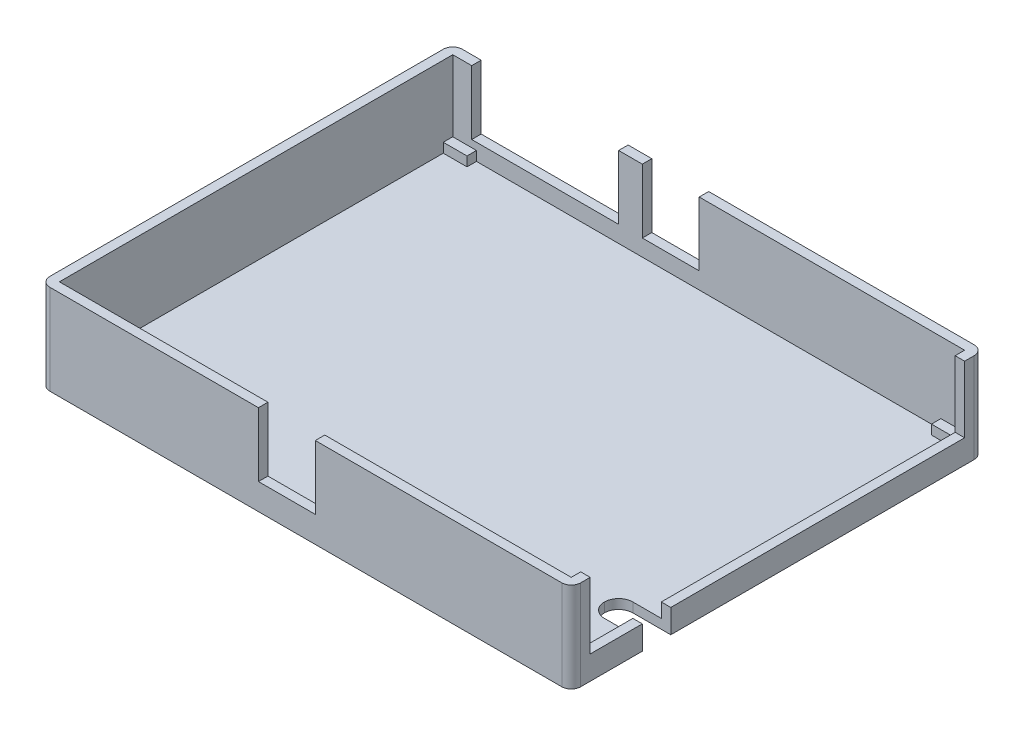
SolidWorks part; units mm, degrees
material "Plain Carbon Steel"
ref_plane "Front Plane" through (0, 0, 0) normal (0, 0, 1) x (1, 0, 0)
ref_plane "Top Plane" through (0, 0, 0) normal (0, 1, 0) x (1, 0, 0)
ref_plane "Right Plane" through (0, 0, 0) normal (1, 0, 0) x (0, 0, -1)
sketch "Sketch1" plane through (0, 0, 0) normal (0, 1, 0) x (1, 0, 0)
  line L1 (0, 0) -> (-112, 0)
  line L2 (0, 0) -> (0, 87)
  line L3 (0, 87) -> (-112, 87)
  line L4 (-112, 0) -> (-112, 87)
  dimension "D1" = 112
  dimension "D2" = 87
extrude "Boss-Extrude1" add sketch "Sketch1" along normal blind 19
sketch "Sketch3" plane through (0, 19, 0) normal (0, 1, 0) x (1, 0, 0)
  line L0 (-112, 87) -> (-112, 0) construction
  line L1 (-110, 85) -> (-2, 85)
  line L2 (-110, 85) -> (-110, 2)
  line L3 (-110, 2) -> (-2, 2)
  line L4 (-2, 85) -> (-2, 2)
  line L5 (0, 87) -> (-112, 87) construction
  line L6 (-112, 0) -> (0, 0) construction
  dimension "D1" = 108
  dimension "D2" = 2
  dimension "D3" = 2
  dimension "D4" = 2
extrude "Cut-Extrude1" cut sketch "Sketch3" against normal blind 17
sketch "Sketch4" plane through (0, 2, 0) normal (0, 1, 0) x (1, 0, 0)
  line L0 (-2, 85) -> (-110, 85) construction
  line L1 (-110, 85) -> (-105, 85)
  line L2 (-110, 85) -> (-110, 83)
  line L3 (-110, 83) -> (-105, 83)
  line L4 (-105, 85) -> (-105, 83)
  line L5 (-110, 85) -> (-110, 2) construction
  dimension "D1" = 0
  dimension "D2" = 0
  dimension "D3" = 5
  dimension "D4" = 2
extrude "Boss-Extrude3" add sketch "Sketch4" along normal blind 2
sketch "Sketch5" plane through (0, 2, 0) normal (0, 1, 0) x (1, 0, 0)
  line L0 (-2, 85) -> (-110, 85) construction
  line L1 (-7, 85) -> (-2, 85)
  line L2 (-7, 85) -> (-7, 83)
  line L3 (-7, 83) -> (-2, 83)
  line L4 (-2, 85) -> (-2, 83)
  line L5 (-2, 2) -> (-2, 85) construction
  dimension "D1" = 5
  dimension "D2" = 2
  dimension "D3" = 0
  dimension "D4" = 0
extrude "Boss-Extrude4" add sketch "Sketch5" along normal blind 2
sketch "Sketch6" plane through (0, 2, 0) normal (0, 1, 0) x (1, 0, 0)
  line L1 (-110, 2) -> (-105, 2)
  line L2 (-110, 2) -> (-110, 4)
  line L3 (-110, 4) -> (-105, 4)
  line L4 (-105, 2) -> (-105, 4)
  dimension "D1" = 5
  dimension "D2" = 2
  dimension "D3" = 0
extrude "Boss-Extrude5" add sketch "Sketch6" along normal blind 2
sketch "Sketch7" plane through (0, 2, 0) normal (0, 1, 0) x (1, 0, 0)
  line L1 (-2, 2) -> (-7, 2)
  line L2 (-2, 2) -> (-2, 4)
  line L3 (-2, 4) -> (-7, 4)
  line L4 (-7, 2) -> (-7, 4)
  dimension "D1" = 5
  dimension "D2" = 2
  dimension "D3" = 0
extrude "Boss-Extrude6" add sketch "Sketch7" along normal blind 2
sketch "Sketch8" plane through (0, 0, 0) normal (0, 0, 1) x (1, 0, 0)
  line L0 (-112, 19) -> (-112, 0) construction
  line L1 (-66, 19) -> (-54, 19)
  line L2 (-66, 19) -> (-66, 5.5)
  line L3 (-66, 5.5) -> (-54, 5.5)
  line L4 (-54, 19) -> (-54, 5.5)
  line L5 (-112, 0) -> (0, 0) construction
  line L8 (-112, 19) -> (0, 19) construction
  dimension "D1" = 46
  dimension "D2" = 12
  dimension "D3" = 5.5
  dimension "D4" = 0
extrude "Cut-Extrude2" cut sketch "Sketch8" against normal blind 2
sketch "Sketch9" plane through (0, 0, -87) normal (0, 0, -1) x (-1, 0, 0)
  line L0 (112, 19) -> (112, 0) construction
  line L1 (106, 19) -> (75, 19)
  line L2 (106, 19) -> (106, 5.5)
  line L3 (106, 5.5) -> (75, 5.5)
  line L4 (75, 19) -> (75, 5.5)
  line L5 (0, 0) -> (112, 0) construction
  line L6 (0, 19) -> (112, 19) construction
  dimension "D1" = 6
  dimension "D2" = 5.5
  dimension "D3" = 0
  dimension "D4" = 31
extrude "Cut-Extrude3" cut sketch "Sketch9" against normal blind 2
sketch "Sketch10" plane through (0, 0, -87) normal (0, 0, -1) x (-1, 0, 0)
  line L0 (75, 19) -> (75, 5.5) construction
  line L1 (70, 19) -> (58, 19)
  line L2 (70, 19) -> (70, 5.5)
  line L3 (70, 5.5) -> (58, 5.5)
  line L4 (58, 19) -> (58, 5.5)
  line L5 (0, 0) -> (112, 0) construction
  line L6 (0, 19) -> (75, 19) construction
  dimension "D1" = 5
  dimension "D2" = 12
  dimension "D3" = 5.5
  dimension "D4" = 0
extrude "Cut-Extrude4" cut sketch "Sketch10" against normal blind 2
fillet "Fillet2" radius 2 1 edges at (-112, 9.5, 0)
fillet "Fillet3" radius 2 1 edges at (0, 9.5, 0)
fillet "Fillet4" radius 2 1 edges at (0, 9.5, -87)
fillet "Fillet5" radius 2 1 edges at (-112, 9.5, -87)
sketch "Sketch11" plane through (0, 2, 0) normal (0, 1, 0) x (1, 0, 0)
  text T0 "MicroBox"
extrude "Cut-Extrude5" cut sketch "Sketch11" against normal blind 0.5
sketch "Sketch13" plane through (0, 0, 0) normal (1, 0, 0) x (0, 0, -1)
  line L0 (2, 19) -> (2, 0) construction
  line L1 (4, 19) -> (83, 19)
  line L2 (4, 19) -> (4, 5)
  line L3 (4, 5) -> (83, 5)
  line L4 (83, 19) -> (83, 5)
  line L5 (85, 0) -> (85, 19) construction
  line L6 (2, 19) -> (85, 19) construction
  line L7 (2, 0) -> (85, 0) construction
  dimension "D1" = 2
  dimension "D2" = 2
  dimension "D3" = 0
  dimension "D4" = 5
extrude "Cut-Extrude6" cut sketch "Sketch13" against normal blind 2
sketch "Sketch14" plane through (0, 0, 0) normal (1, 0, 0) x (0, 0, -1)
  line L0 (4, 5) -> (83, 5) construction
  line L1 (15, 5) -> (21, 5)
  line L2 (15, 5) -> (15, 0)
  line L3 (15, 0) -> (21, 0)
  line L4 (21, 5) -> (21, 0)
  line L5 (2, 0) -> (85, 0) construction
  line L6 (2, 19) -> (2, 0) construction
  dimension "D1" = 13
  dimension "D2" = 19
extrude "Cut-Extrude8" cut sketch "Sketch14" against normal blind 11
fillet "Fillet6" radius 3 2 edges at (-11, 1, -21) (-11, 1, -15)
